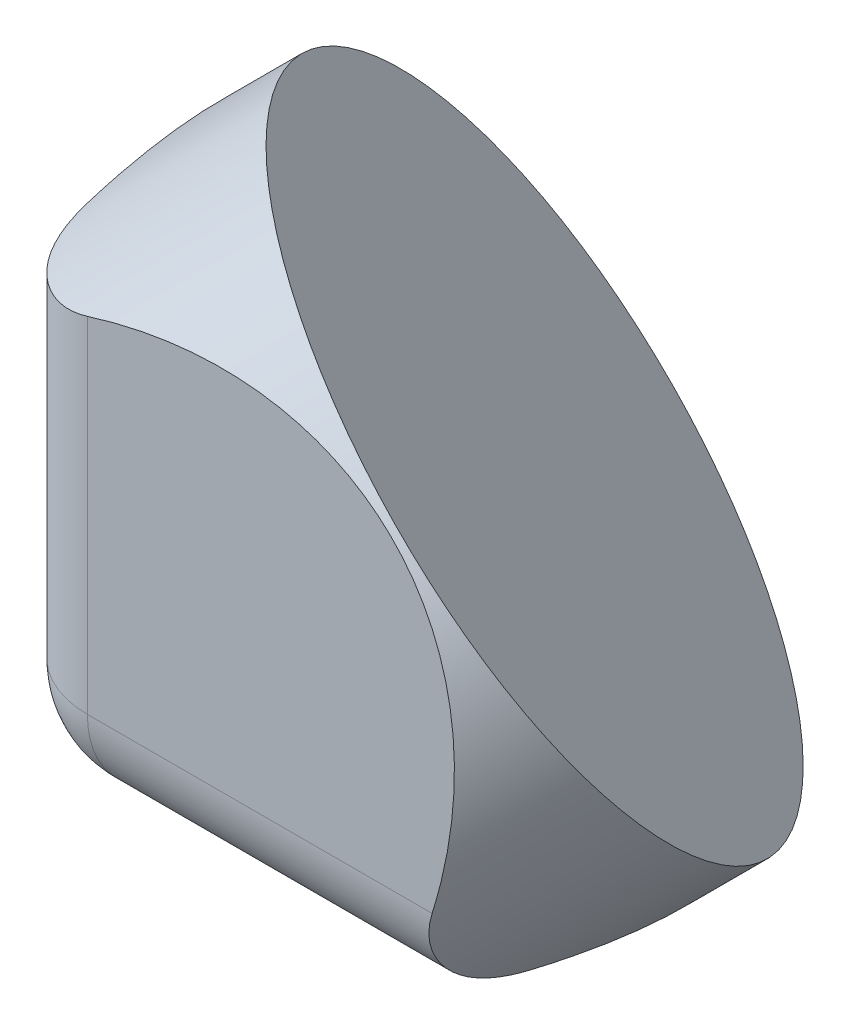
SolidWorks part; units mm, degrees
ref_plane "Front" through (0, 0, 0) normal (0, 0, 1) x (1, 0, 0)
ref_plane "Top" through (0, 0, 0) normal (0, 1, 0) x (1, 0, 0)
ref_plane "Right" through (0, 0, 0) normal (1, 0, 0) x (0, 0, -1)
sketch "Sketch1" plane through (0, 0, 0) normal (0, 1, 0) x (1, 0, 0)
  line L1 (0, 0) -> (60.6, 0)
  line L2 (0, 0) -> (0, 60.6)
  line L3 (0, 60.6) -> (60.6, 60.6)
  line L4 (60.6, 0) -> (60.6, 60.6)
  dimension "D1" = 60.6
  dimension "D2" = 60.6
extrude "Extrude1" add sketch "Sketch1" along normal blind 60.6
sketch3d "3DSketch1"
  line L0 (60.6, 60.6, -60.6) -> (0, 0, 0) construction
ref_plane "Plane1" through (0, 0, 0) normal (-0.5774, -0.5774, 0.5774) x (0.8165, -0.4082, 0.4082)
ref_plane "Plane2" through (30.2993, 30.2993, -30.2993) normal (-0.5774, -0.5774, 0.5774) x (0.8165, -0.4082, 0.4082)
sketch "Sketch4" plane through (30.2993, 30.2993, -30.2993) normal (-0.5774, -0.5774, 0.5774) x (0.8165, -0.4082, 0.4082)
  line L0 (-49.4797, 0) -> (-24.7398, -42.8507) construction
  line L1 (-49.4797, 0) -> (-24.7398, -42.8507)
  line L2 (24.7398, -42.8507) -> (-24.7398, -42.8507) construction
  line L3 (24.7398, -42.8507) -> (-24.7398, -42.8507)
  line L4 (49.4797, 0) -> (24.7398, -42.8507) construction
  line L5 (49.4797, 0) -> (24.7398, -42.8507)
  line L6 (24.7398, 42.8507) -> (49.4797, 0) construction
  line L7 (24.7398, 42.8507) -> (49.4797, 0)
  line L8 (-24.7398, 42.8507) -> (24.7398, 42.8507) construction
  line L9 (-24.7398, 42.8507) -> (24.7398, 42.8507)
  line L10 (-49.4797, 0) -> (-24.7398, 42.8507) construction
  line L11 (-49.4797, 0) -> (-24.7398, 42.8507)
extrude "Cut-Extrude2" cut sketch "Sketch4" against normal through all
sketch "Sketch3" plane through (30.2993, 30.2993, -30.2993) normal (-0.5774, -0.5774, 0.5774) x (0.8165, -0.4082, 0.4082)
  line L1 (-37.109, 21.4267) -> (-24.7398, 42.8507) construction
  line L3 (-24.7398, 42.8507) -> (-0.0016, 42.8507) construction
  line L5 (37.1106, 21.4239) -> (49.4797, 0) construction
  line L7 (49.4797, 0) -> (37.1106, -21.4239) construction
  line L9 (37.1106, 21.4239) -> (-0.0016, 42.8507) construction
  line L11 (37.1106, -21.4239) -> (-0.0016, -42.8507) construction
  line L12 (-0.0016, -42.8507) -> (-24.7398, -42.8507) construction
  line L13 (-37.109, -21.4267) -> (-24.7398, -42.8507) construction
  line L14 (-37.109, 21.4267) -> (-37.109, -21.4267) construction
  line L15 (-37.109, 21.4267) -> (-24.7398, 42.8507)
  line L16 (-24.7398, 42.8507) -> (-0.0016, 42.8507)
  line L17 (37.1106, 21.4239) -> (49.4797, 0)
  line L18 (49.4797, 0) -> (37.1106, -21.4239)
  line L19 (37.1106, 21.4239) -> (-0.0016, 42.8507)
  line L20 (37.1106, -21.4239) -> (-0.0016, -42.8507)
  line L21 (-0.0016, -42.8507) -> (-24.7398, -42.8507)
  line L22 (-37.109, -21.4267) -> (-24.7398, -42.8507)
  line L23 (-37.109, 21.4267) -> (-37.109, -21.4267)
  circle A0 centre (0, 0) radius 36.55
  dimension "D1" = 73.1
extrude "Cut-Extrude1" cut sketch "Sketch3" along normal through all
sketch3d "3DSketch4"
  line L0 (30.2993, 30.2993, -30.2993) -> (-6.1124, -6.1124, 6.1124) construction
  line L1 (14.9215, 14.9215, -14.9215) -> (30.2993, 30.2993, -30.2993) construction
ref_plane "Plane3" through (0, 0, 0) normal (0, 0.7071, 0.7071) x (1, 0, 0)
sketch "Sketch14" plane through (0, 0, 0) normal (-1, 0, 0) x (0, 0, 1)
  line L0 (0, 0) -> (-65.6, 65.6) construction
  line L1 (-26.103, 16.6321) -> (-32.8, 32.8) construction
  circle A0 centre (-32.8, 32.8) radius 17.5 construction
  circle A1 centre (-26.103, 16.6321) radius 3
  circle A2 centre (-48.9679, 26.103) radius 3
  circle A3 centre (-39.497, 48.9679) radius 3
  circle A4 centre (-16.6321, 39.497) radius 3
  dimension "D3" = 35
  dimension "D4" = 6
  dimension "D1" = 65.6
  dimension "D2" = 65.6
  dimension "D5" = 22.5
extrude "Extrude5" [suppressed] add sketch "Sketch14" along normal blind 0.6
fillet "Fillet1" radius 10.9 3 edges at (0, 0, -22.3822) (0, 22.3822, 0) (22.3822, 0, 0)
